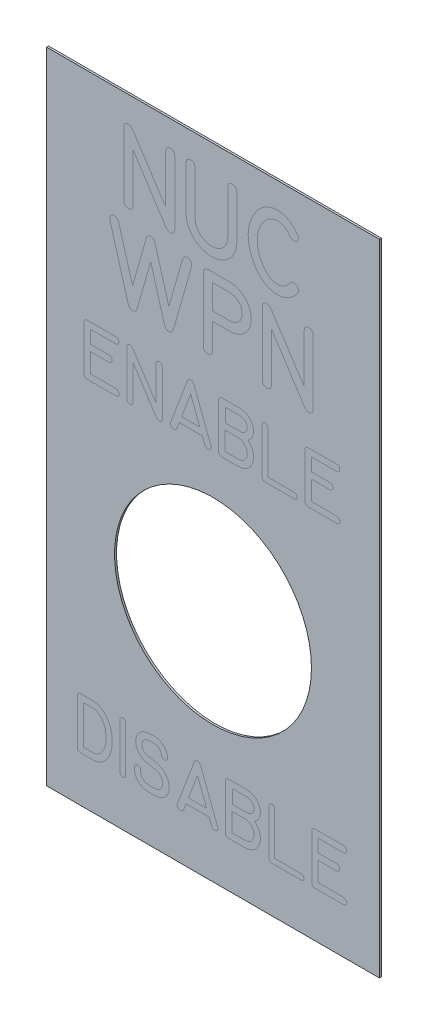
SolidWorks part; units mm, degrees
material "Acrylic (Medium-high impact)"
ref_plane "Front" through (0, 0, 0) normal (0, 0, 1) x (1, 0, 0)
ref_plane "Top" through (0, 0, 0) normal (0, 1, 0) x (1, 0, 0)
ref_plane "Right" through (0, 0, 0) normal (1, 0, 0) x (0, 0, -1)
sketch "Sketch1" plane through (0, 0, 0) normal (0, 0, 1) x (1, 0, 0)
  line L1 (-11.4889, -53.233) -> (-32.9611, -53.233)
  line L2 (-11.4889, -53.233) -> (-11.4889, -11.958)
  line L3 (-11.4889, -11.958) -> (-32.9611, -11.958)
  line L4 (-32.9611, -53.233) -> (-32.9611, -11.958)
  line L5 (-11.4889, -53.233) -> (-32.9611, -11.958) construction
  line L6 (-11.4889, -11.958) -> (-32.9611, -53.233) construction
  circle A0 centre (-22.225, -38.1) radius 6.35
  circle A1 centre (-22.225, -38.1) radius 6.35 construction
  point P0 (-22.225, -32.5955)
  point P5 (-22.225, -38.1)
  dimension "D1" = 41.275
extrude "Boss-Extrude1" add sketch "Sketch1" along normal blind 0.127
sketch "Sketch2" plane through (0, 0, 0.127) normal (0, 0, 1) x (1, 0, 0)
  line L0 (-22.225, -31.75) -> (-22.225, -29.21) construction
  line L1 (-32.9611, -29.21) -> (-11.4889, -29.21) construction
  line L2 (-11.4889, -53.233) -> (-11.4889, -11.958) construction
  line L3 (-32.9611, -50.292) -> (-11.4889, -50.292) construction
  line L4 (-22.225, -44.45) -> (-22.225, -50.292) construction
  line L5 (-32.9611, -23.9006) -> (-11.4889, -23.9006) construction
  line L6 (-32.9611, -11.958) -> (-32.9611, -53.233) construction
  line L7 (-32.9611, -18.3433) -> (-11.4889, -18.3433) construction
  circle A0 centre (-22.225, -38.1) radius 6.35 construction
  text T0 "ENABLE"
  text T1 "DISABLE"
  text T2 "NUC" font "GordonURWMed" height in points 20
  text T3 "WPN" font "GordonURWMed" height in points 20
  point P10 (-22.225, -29.21)
  point P13 (-22.225, -50.292)
  dimension "D1" = 2.54
  dimension "D2" = 5.842
wrap "Wrap1" sketch "Sketch2" wrap type scribe source sketch "Sketch2"
